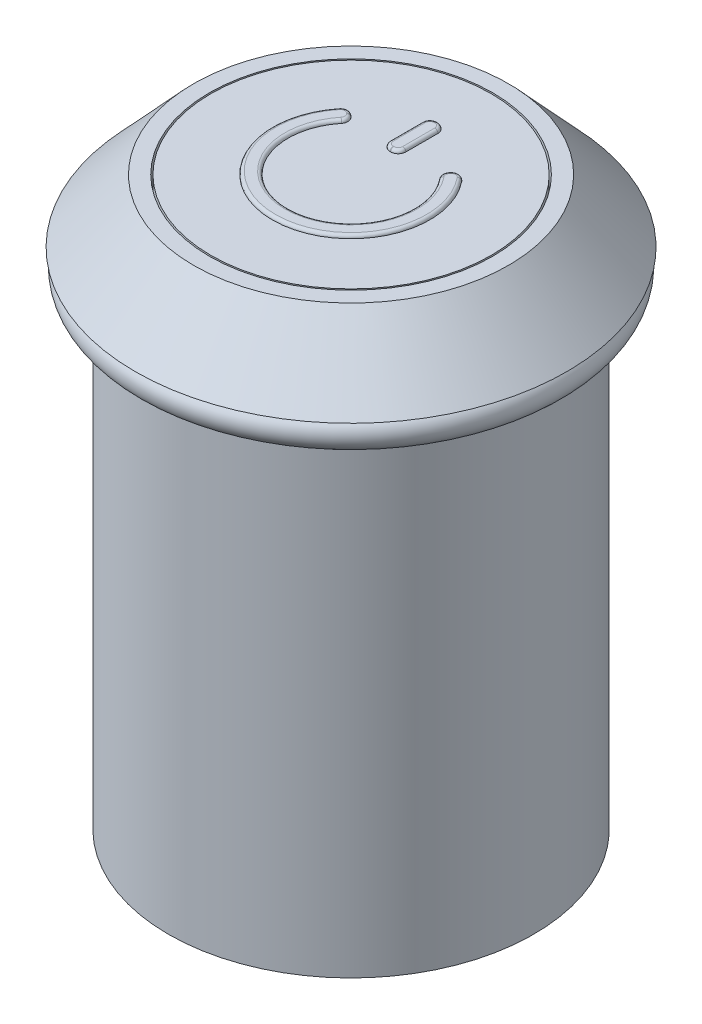
SolidWorks part; units mm, degrees
material "6061 Alloy"
ref_plane "Front Plane" through (0, 0, 0) normal (0, 0, 1) x (1, 0, 0)
ref_plane "Top Plane" through (0, 0, 0) normal (0, 1, 0) x (1, 0, 0)
ref_plane "Right Plane" through (0, 0, 0) normal (1, 0, 0) x (0, 0, -1)
sketch "Sketch1" plane through (0, 0, 0) normal (0, 1, 0) x (1, 0, 0)
  circle A0 centre (0, 0) radius 5.8
  dimension "D1" = 11.6
extrude "Boss-Extrude1" add sketch "Sketch1" along normal blind 16
sketch "Sketch2" plane through (0, 16, 0) normal (0, 1, 0) x (1, 0, 0)
  circle A0 centre (0, 0) radius 6.85
  dimension "D1" = 13.7
ref_plane "Plane1" through (0, 18, 0) normal (0, 1, 0) x (1, 0, 0)
sketch "Sketch3" plane through (0, 18, 0) normal (0, 1, 0) x (1, 0, 0)
  circle A0 centre (0, 0) radius 5
  dimension "D1" = 10
loft "Loft1" add profiles "Sketch3", "Sketch2" connector at (-3.1968, 18, 3.8445) connector at (-4.1944, 16, 5.4157)
sketch "Sketch4" plane through (0, 18, 0) normal (0, 1, 0) x (1, 0, 0)
  circle A0 centre (0, 0) radius 4.5
  dimension "D1" = 9
extrude "Cut-Extrude1" cut sketch "Sketch4" against normal blind 3
sketch "Sketch6" plane through (0, 15, 0) normal (0, 1, 0) x (1, 0, 0)
  circle A0 centre (0, 0) radius 4.45
  dimension "D1" = 8.9
extrude "Boss-Extrude2" add sketch "Sketch6" along normal blind 3
sketch "Sketch7" plane through (0, 18, 0) normal (0, 1, 0) x (1, 0, 0)
  line L0 (-1.589, 1.589) -> (-1.5748, 1.5748)
  line L1 (1.5748, 1.5748) -> (1.589, 1.589)
  line L2 (0, 0) -> (0, 50000) construction
  line L4 (-0.01, 2.75) -> (0.01, 2.75)
  line L5 (-0.25, 2.51) -> (-0.25, 1.49)
  line L6 (-0.01, 1.25) -> (0.01, 1.25)
  line L7 (0.25, 2.51) -> (0.25, 1.49)
  line L8 (-0.25, 2.75) -> (0.25, 1.25) construction
  line L9 (-0.25, 1.25) -> (0.25, 2.75) construction
  arc A0 (-1.9455, 1.57) -> (1.9455, 1.57) centre (0, 0) ccw
  arc A1 (-1.5576, 1.2545) -> (1.5576, 1.2545) centre (0, 0) ccw
  arc A2 (1.5576, 1.2545) -> (1.5748, 1.5748) centre (1.7445, 1.4051) cw
  arc A3 (-1.5576, 1.2545) -> (-1.5748, 1.5748) centre (-1.7445, 1.4051) ccw
  arc A4 (-1.589, 1.589) -> (-1.9455, 1.57) centre (-1.7587, 1.4193) ccw
  arc A5 (1.589, 1.589) -> (1.9455, 1.57) centre (1.7587, 1.4193) cw
  arc A6 (-0.25, 1.49) -> (-0.01, 1.25) centre (-0.01, 1.49) ccw
  arc A7 (0.01, 1.25) -> (0.25, 1.49) centre (0.01, 1.49) ccw
  arc A8 (0.01, 2.75) -> (0.25, 2.51) centre (0.01, 2.51) cw
  arc A9 (-0.01, 2.75) -> (-0.25, 2.51) centre (-0.01, 2.51) ccw
  point P13 (1.4142, 1.4142)
  point P16 (-1.4142, 1.4142)
  point P21 (0, 2)
  dimension "D1" = 5
  dimension "D2" = 4
  dimension "D5" = 0.24
  dimension "D6" = 0.24
  dimension "D10" = 0.24
  dimension "D3" = 45
  dimension "D4" = 45
  dimension "D7" = 0.5
  dimension "D8" = 2
  dimension "D9" = 1.5
extrude "Boss-Extrude3" add sketch "Sketch7" along normal blind 0.1
fillet "Fillet1" radius 0.1 16 edges at (-1.7715, 18.1, -1.659) (-1.5819, 18.1, -1.5819) (-1.5049, 18.1, -1.418) (0, 18.1, 2) (1.5049, 18.1, -1.418) (1.5819, 18.1, -1.5819) (1.7715, 18.1, -1.659) (-0.25, 18.1, -2) (-0.1797, 18.1, -2.6797) (0, 18.1, -2.75) (0.1797, 18.1, -2.6797) (0.25, 18.1, -2) (0.1797, 18.1, -1.3203) (0, 18.1, -1.25) (-0.1797, 18.1, -1.3203) (0, 18.1, 2.5)
sketch "Sketch8" plane through (0, 0, 0) normal (0, 0, 1) x (1, 0, 0)
  line L0 (-6.85, 16) -> (6.85, 16) construction
  line L1 (-5.8, 16) -> (-5.8, 0) construction
  line L2 (0, 16) -> (0, 50016) construction
  line L3 (-5.8, 16) -> (5.8, 16) construction
  circle A0 centre (-6.3, 15.5) radius 0.5
  point P10 (0, 16)
  dimension "D1" = 1
revolve "Revolve1" add sketch "Sketch8" angle 360 about L2
